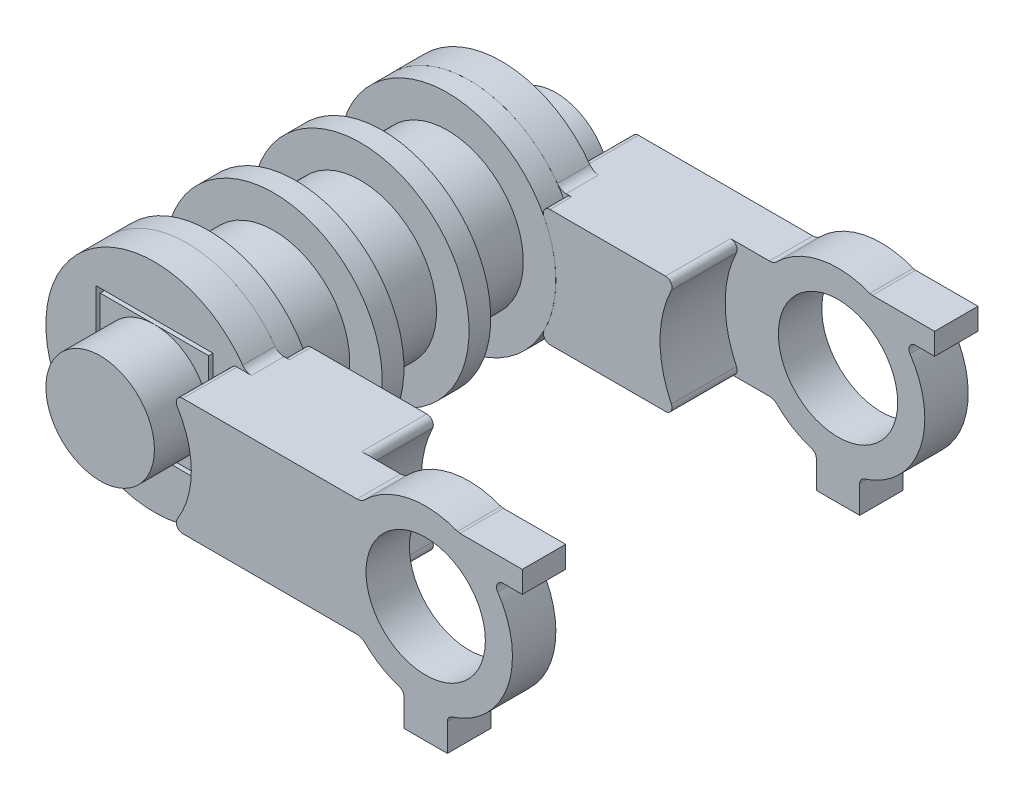
SolidWorks part; units mm, degrees
ref_plane "正面" through (0, 0, 0) normal (0, 0, 1) x (1, 0, 0)
ref_plane "平面" through (0, 0, 0) normal (0, 1, 0) x (1, 0, 0)
ref_plane "右側面" through (0, 0, 0) normal (1, 0, 0) x (0, 0, -1)
sketch "ｽｹｯﾁ1" plane through (0, 0, 0) normal (0, 0, 1) x (1, 0, 0)
  circle A0 centre (0, 0) radius 3.5
  dimension "D1" = 7
extrude "ﾎﾞｽ - 押し出し1" add sketch "ｽｹｯﾁ1" along normal blind 3
sketch "ｽｹｯﾁ2" plane through (0, 0, 0) normal (0, 0, -1) x (-1, 0, 0)
  circle A0 centre (0, 0) radius 5
  dimension "D1" = 10
extrude "ﾎﾞｽ - 押し出し2" add sketch "ｽｹｯﾁ2" along normal blind 1
sketch "ｽｹｯﾁ3" plane through (0, 0, -1) normal (0, 0, -1) x (-1, 0, 0)
  circle A0 centre (0, 0) radius 3.5 construction
  circle A1 centre (0, 0) radius 3.5
extrude "ﾎﾞｽ - 押し出し3" add sketch "ｽｹｯﾁ3" along normal blind 3
sketch "ｽｹｯﾁ4" plane through (0, 0, -4) normal (0, 0, -1) x (-1, 0, 0)
  circle A1 centre (0, 0) radius 5
  circle A2 centre (0, 0) radius 5
  dimension "D1" = 0
extrude "ﾎﾞｽ - 押し出し4" add sketch "ｽｹｯﾁ4" along normal blind 1
sketch "ｽｹｯﾁ5" plane through (0, 0, -5) normal (0, 0, -1) x (-1, 0, 0)
  circle A0 centre (0, 0) radius 3.5 construction
  circle A1 centre (0, 0) radius 3.5
extrude "ﾎﾞｽ - 押し出し5" add sketch "ｽｹｯﾁ5" along normal blind 3
sketch "ｽｹｯﾁ6" plane through (0, 0, -8) normal (0, 0, -1) x (-1, 0, 0)
  circle A1 centre (0, 0) radius 5
  circle A2 centre (0, 0) radius 5
  dimension "D1" = 0
extrude "ﾎﾞｽ - 押し出し6" add sketch "ｽｹｯﾁ6" along normal blind 1
sketch "ｽｹｯﾁ7" plane through (0, 0, 3) normal (0, 0, 1) x (1, 0, 0)
  circle A1 centre (0, 0) radius 5
  circle A2 centre (0, 0) radius 5
  dimension "D1" = 0
extrude "ﾎﾞｽ - 押し出し7" add sketch "ｽｹｯﾁ7" along normal blind 1
sketch "ｽｹｯﾁ10" plane through (0, 0, 4) normal (0, 0, 1) x (1, 0, 0)
  line L1 (2.5, -2.5) -> (-2.5, -2.5)
  line L2 (2.5, -2.5) -> (2.5, 2.5)
  line L3 (2.5, 2.5) -> (-2.5, 2.5)
  line L4 (-2.5, -2.5) -> (-2.5, 2.5)
  line L5 (2.5, -2.5) -> (-2.5, 2.5) construction
  line L6 (2.5, 2.5) -> (-2.5, -2.5) construction
  point P0 (0, 0)
  dimension "D1" = 5
  dimension "D2" = 5
extrude "ﾎﾞｽ - 押し出し10" add sketch "ｽｹｯﾁ10" along normal blind 1.5
sketch "ｽｹｯﾁ11" plane through (0, 0, 5.5) normal (0, 0, 1) x (1, 0, 0)
  circle A0 centre (0, 0) radius 2.5
  dimension "D1" = 5
extrude "ﾎﾞｽ - 押し出し11" add sketch "ｽｹｯﾁ11" along normal blind 2.5
ref_plane "平面1" through (0, 0, -2.5) normal (0, 0, 1) x (1, 0, 0)
mirror "ﾐﾗｰ1" about plane through (0, 0, -2.5) normal (0, 0, 1) of "ﾎﾞｽ - 押し出し11", "ﾎﾞｽ - 押し出し10"
sketch "ｽｹｯﾁ12" plane through (0, 0, 4) normal (0, 0, 1) x (1, 0, 0)
  line L0 (0, 0) -> (15, 0) construction
  line L1 (4.2083, 2.7) -> (10.5559, 2.7)
  line L3 (10.5559, -2.7) -> (4.2083, -2.7)
  line L8 (2.7, -2.7) -> (2.7, 2.7)
  line L9 (-2.7, -2.7) -> (2.7, -2.7)
  line L10 (-2.7, 2.7) -> (-2.7, -2.7)
  line L11 (2.7, 2.7) -> (-2.7, 2.7)
  line L12 (2.7, -2.7) -> (2.7, 2.7)
  line L13 (-2.7, -2.7) -> (2.7, -2.7)
  line L14 (-2.7, 2.7) -> (-2.7, -2.7)
  line L15 (2.7, 2.7) -> (-2.7, 2.7)
  circle A0 centre (0, 0) radius 5 construction
  circle A1 centre (15, 0) radius 2.75 construction
  arc A2 (4.2083, 2.7) -> (4.2083, -2.7) centre (0, 0) ccw
  circle A3 centre (15, 0) radius 4 construction
  circle A4 centre (15, 0) radius 5.2 construction
  arc A5 (10.5559, 2.7) -> (10.5559, -2.7) centre (15, 0) ccw
  circle A6 centre (15, 0) radius 5 construction
  circle A7 centre (0, 0) radius 5 construction
  dimension "D4" = 5.5
  dimension "D5" = 1.25
  dimension "D6" = 0.2
  dimension "D3" = 15
  dimension "D1" = 0.2
extrude "ﾎﾞｽ - 押し出し12" add sketch "ｽｹｯﾁ12" along normal blind 1.5 separate body
sketch "ｽｹｯﾁ13" plane through (0, 0, 5.5) normal (0, 0, 1) x (1, 0, 0)
  line L0 (4.2083, 2.7) -> (10.5559, 2.7) construction
  line L1 (10.5559, 2.7) -> (3.2171, 2.7)
  line L3 (10.5559, -2.7) -> (3.2171, -2.7)
  line L5 (10.5559, 2.7) -> (3.2171, -2.7) construction
  line L6 (10.5559, -2.7) -> (3.2171, 2.7) construction
  line L7 (10.5559, -2.7) -> (4.2083, -2.7) construction
  circle A0 centre (0, 0) radius 4 construction
  circle A1 centre (15, 0) radius 4 construction
  circle A2 centre (0, 0) radius 4.2 construction
  arc A3 (3.2171, -2.7) -> (3.2171, 2.7) centre (0, 0) ccw
  circle A4 centre (15, 0) radius 5.2 construction
  arc A5 (10.5559, 2.7) -> (10.5559, -2.7) centre (15, 0) ccw
  arc A6 (10.5559, 2.7) -> (10.5559, -2.7) centre (15, 0) ccw construction
  point P4 (6.8865, 0)
  point P14 (0, 0)
  dimension "D1" = 0.2
extrude "ﾎﾞｽ - 押し出し13" add sketch "ｽｹｯﾁ13" along normal blind 0.5
sketch "ｽｹｯﾁ14" plane through (0, 0, 6) normal (0, 0, 1) x (1, 0, 0)
  line L1 (3.2171, -2.7) -> (12.0487, -2.7)
  line L2 (3.2171, 2.7) -> (12.0487, 2.7)
  line L4 (4.2083, 2.7) -> (10.5559, 2.7) construction
  line L5 (10.5559, -2.7) -> (4.2083, -2.7) construction
  circle A0 centre (15, 0) radius 4 construction
  circle A1 centre (15, 0) radius 2.75 construction
  circle A2 centre (15, 0) radius 2.75
  arc A3 (12.0487, 2.7) -> (12.0487, -2.7) centre (15, 0) cw
  arc A5 (3.2171, -2.7) -> (3.2171, 2.7) centre (0, 0) ccw construction
  arc A6 (3.2171, -2.7) -> (3.2171, 2.7) centre (0, 0) ccw
  point P4 (0, 0)
  point P5 (10.7917, 2.7)
  point P13 (4.9642, 2.7)
  point P14 (4.9802, -2.7)
  point P19 (0, 0)
  point P21 (0, 0)
extrude "ﾎﾞｽ - 押し出し14" add sketch "ｽｹｯﾁ14" along normal blind 2
sketch "ｽｹｯﾁ15" plane through (0, 0, 4) normal (0, 0, -1) x (-1, 0, 0)
  line L0 (-10.5559, 2.7) -> (-4.7255, 2.7)
  line L1 (-4.2083, 2.7) -> (-10.5559, 2.7) construction
  line L2 (-10.5559, -2.7) -> (-4.7255, -2.7)
  line L3 (-10.5559, -2.7) -> (-4.2083, -2.7) construction
  line L4 (-10.5559, 2.7) -> (-4.2083, 2.7) construction
  line L5 (-4.2083, -2.7) -> (-10.5559, -2.7) construction
  circle A2 centre (0, 0) radius 5 construction
  arc A3 (-4.458, 2.2642) -> (-4.458, -2.2642) centre (0, 0) ccw
  circle A4 centre (-15, 0) radius 5 construction
  circle A5 centre (-15, 0) radius 5.2 construction
  arc A6 (-10.5559, -2.7) -> (-10.5559, 2.7) centre (-15, 0) ccw
  arc A7 (-4.7255, -2.7) -> (-4.458, -2.2642) centre (-4.7255, -2.4) ccw
  arc A8 (-4.7255, 2.7) -> (-4.458, 2.2642) centre (-4.7255, 2.4) cw
  point P21 (-10.5559, -2.7)
  point P22 (-10.5559, 2.7)
  point P23 (0, 0)
  point P26 (-4.2083, -2.7)
  point P29 (-4.2083, 2.7)
  dimension "D2" = 0.3
  dimension "D1" = 0.2
extrude "ﾎﾞｽ - 押し出し15" add sketch "ｽｹｯﾁ15" along normal blind 1
sketch "ｽｹｯﾁ16" plane through (0, 0, 8) normal (0, 0, 1) x (1, 0, 0)
  line L0 (15, 0) -> (15, -4.623) construction
  line L1 (14, -3.873) -> (16, -3.873)
  line L2 (14, -3.873) -> (14, -5.373)
  line L3 (14, -5.373) -> (16, -5.373)
  line L4 (16, -3.873) -> (16, -5.373)
  line L5 (14, -3.873) -> (16, -5.373) construction
  line L6 (14, -5.373) -> (16, -3.873) construction
  line L7 (12.0487, 2.7) -> (17.9513, 2.7) construction
  line L9 (16.5199, 2.7) -> (19.4513, 2.7)
  line L10 (16.5199, 2.7) -> (16.5199, 3.7)
  line L11 (16.5199, 3.7) -> (19.4513, 3.7)
  line L12 (19.4513, 2.7) -> (19.4513, 3.7)
  line L13 (16.5199, 2.7) -> (19.4513, 3.7) construction
  line L14 (16.5199, 3.7) -> (19.4513, 2.7) construction
  arc A0 (12.0487, -2.7) -> (12.0487, 2.7) centre (15, 0) ccw construction
  point P4 (15, -4.623)
  point P18 (17.9856, 3.2)
  point P19 (16.7641, 3.59)
  point P20 (0, 0)
  point P21 (16.4315, 3.7351)
  dimension "D1" = 2
  dimension "D2" = 1.5
  dimension "D3" = 1
  dimension "D4" = 1.5
extrude "ﾎﾞｽ - 押し出し16" add sketch "ｽｹｯﾁ16" against normal up to surface (2 mm away) up to face at (17.75, 0, 6)
fillet "ﾌｨﾚｯﾄ8" radius 0.3 4 edges at (14, -3.873, 7) (16, -3.873, 7) (17.9513, 2.7, 7) (16.5199, 3.7, 7)
fillet "ﾌｨﾚｯﾄ5" radius 0.5 4 edges at (4.2083, -2.7, 4.75) (12.0487, -2.7, 7) (12.0487, 2.7, 7) (4.2083, 2.7, 4.75)
fillet "ﾌｨﾚｯﾄ3" radius 0.3 4 edges at (10.5559, -2.7, 4.5) (10.5559, 2.7, 4.5) (3.2171, -2.7, 6.75) (3.2171, 2.7, 6.75)
mirror "ﾐﾗｰ2" about plane through (0, 0, -2.5) normal (0, 0, 1) of bodies 118 116
